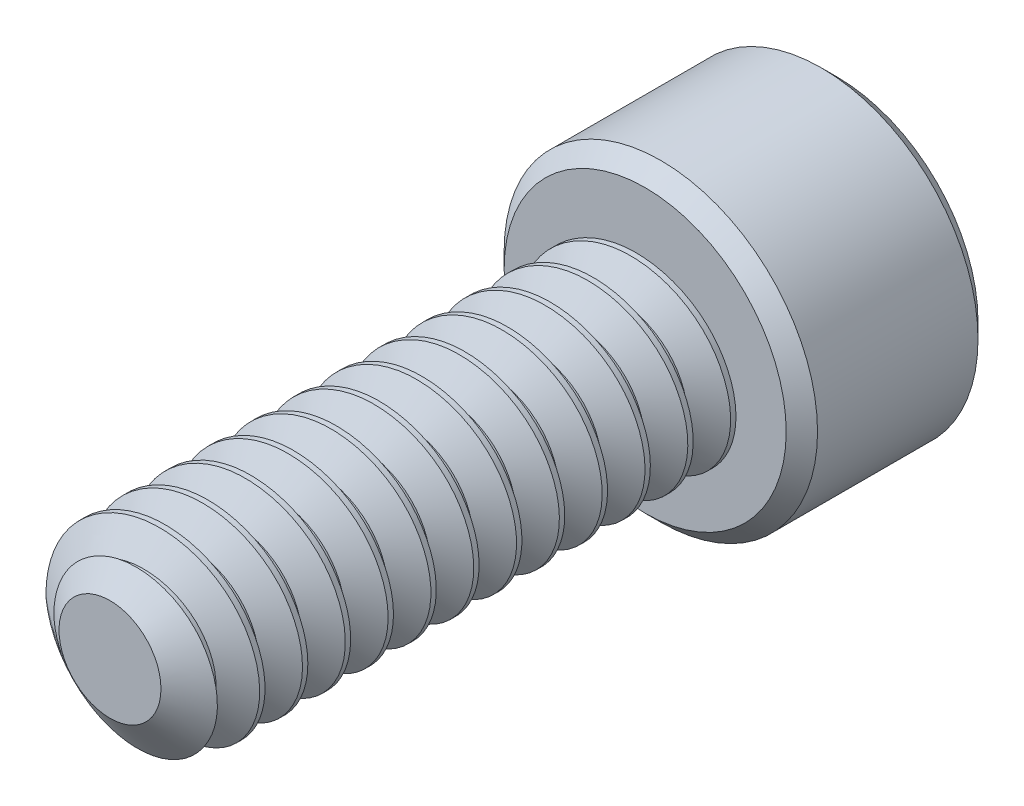
SolidWorks part; units mm, degrees
material "Alloy Steel"
ref_plane "Front Plane" through (0, 0, 0) normal (0, 0, 1) x (1, 0, 0)
ref_plane "Top Plane" through (0, 0, 0) normal (0, 1, 0) x (1, 0, 0)
ref_plane "Right Plane" through (0, 0, 0) normal (1, 0, 0) x (0, 0, -1)
sketch "Sketch1" plane through (0, 0, 0) normal (0, 0, 1) x (1, 0, 0)
  circle A0 centre (0, 0) radius 1.4224
  dimension "OD" = 2.8448
extrude "Extrude1" add sketch "Sketch1" against normal blind 7.9375
sketch "Sketch2" plane through (0, 0, 0) normal (0, 0, 1) x (1, 0, 0)
  circle A0 centre (0, 0) radius 1.4224 construction
  circle A1 centre (0, 0) radius 1.4224
curve "Helix/Spiral1" pitch 0.635 height 8.5725 radius 1.4224 centre (0, 0, 0) axis (0, 0, -1) start towards (0, 1, 0) parameters "pitch"=0.635
sketch "Sketch3" plane through (0, 0, 0) normal (1, 0, 0) x (0, 0, -1)
  line L0 (-0.5556, 1.4224) -> (-0.3175, 1.01)
  line L1 (-0.3175, 1.01) -> (-0.2381, 1.01)
  line L2 (-0.2381, 1.01) -> (0, 1.4224)
  line L3 (-0.5556, 1.4224) -> (0, 1.4224)
  line L4 (-0.2778, 1.4224) -> (-0.2778, 1.01) construction
  line L5 (-0.4366, 1.2162) -> (-0.1191, 1.2162) construction
  line L6 (0, 1.4224) -> (0, -1.4224) construction
  dimension "D1" = 0.0794
  dimension "D2" = 0.3175
  dimension "D3" = 60
sweep "Cut-Sweep1" cut profiles "Sketch3" path "Helix/Spiral1"
sketch "Sketch4" plane through (0, 0, 0) normal (1, 0, 0) x (0, 0, -1)
  line L0 (0.4666, 1.4224) -> (0, 0.756)
  line L1 (0, 0.756) -> (0, 1.4224)
  line L2 (0.4666, 1.4224) -> (0, 1.4224)
  line L3 (-0.5556, 1.4224) -> (0, 1.4224) construction
  line L4 (0, 0) -> (7.0209, 0) construction
  dimension "D1" = 55
  dimension "D2" = 0.254
revolve "Cut-Revolve1" cut sketch "Sketch4" angle 360 about L4
sketch "Sketch5" plane through (0, 0, 0) normal (1, 0, 0) x (0, 0, -1)
  line L0 (7.9375, -1.0149) -> (7.9375, 1.0232) construction
  line L1 (7.9375, 1.5494) -> (38.1885, 1.5494)
  line L2 (7.9375, 1.5494) -> (7.9375, 0)
  line L3 (7.9375, 0) -> (38.1, 0)
  line L4 (38.1, 1.2192) -> (38.1, 0)
  line L5 (38.1885, 1.5494) -> (38.1, 1.2192)
  line L6 (0, 0) -> (9.9695, 0) construction
  point P3 (38.1, 1.5494)
  point P10 (38.1, 1.5494)
  dimension "D1" = 0.3302
  dimension "Thread min" = 38.1
  dimension "D2" = 0.127
  dimension "D3" = 15
revolve "partially thread" [suppressed] add sketch "Sketch5" angle 360 about L6
sketch "Sketch6" plane through (0, 0, -7.9375) normal (0, 0, -1) x (-1, 0, 0)
  circle A0 centre (0, 0) radius 2.3241
  dimension "head dia" = 4.6482
extrude "Extrude2" add sketch "Sketch6" along normal blind 2.8448
sketch "Sketch7" plane through (0, 0, -10.7823) normal (0, 0, -1) x (-1, 0, 0)
  line L1 (0, 1.3748) -> (-1.1906, 0.6874)
  line L2 (-1.1906, 0.6874) -> (-1.1906, -0.6874)
  line L3 (-1.1906, -0.6874) -> (0, -1.3748)
  line L4 (0, -1.3748) -> (1.1906, -0.6874)
  line L5 (1.1906, -0.6874) -> (1.1906, 0.6874)
  line L6 (1.1906, 0.6874) -> (0, 1.3748)
  circle A0 centre (0, 0) radius 1.1906 construction
  dimension "hex dia" = 2.3813
extrude "Cut-Extrude1" cut sketch "Sketch7" against normal blind 1.7859
sketch "Sketch8" plane through (0, 0, -10.7823) normal (0, 0, -1) x (-1, 0, 0)
  circle A0 centre (0, 0) radius 1.3748
extrude "Cut-Extrude2" cut sketch "Sketch8" against normal through all draft 45
chamfer "Chamfer1" distance 0.2324 angle 45 2 edges at (-2.3241, 0, -10.7823) (-2.3241, 0, -7.9375)
sketch "Sketch9" plane through (0, 0, 0) normal (1, 0, 0) x (0, 0, -1)
  line L0 (0, 1.4224) -> (0, -1.4224) construction
  line L1 (6.6675, 1.4224) -> (6.6675, -1.4224) construction
  dimension "D1" = 6.6675
  dimension "D4" = 0.635
  dimension "D5" = 0.3302
equation "\"D3@Helix/Spiral1\" = \"screw length@Extrude1\"+\"pitch@Helix/Spiral1\""
equation "\"D1@Sketch3\" = \"pitch@Helix/Spiral1\"*.125"
equation "\"D2@Sketch3\" = \"pitch@Helix/Spiral1\"*.5"
equation "\"D1@Cut-Extrude1\" = \"hex dia@Sketch7\"*.75"
equation "\"D1@Chamfer1\" = \"head dia@Sketch6\"*.05"
equation "\"D1@Sketch9\" = \"pitch@Helix/Spiral1\"*10.5"
